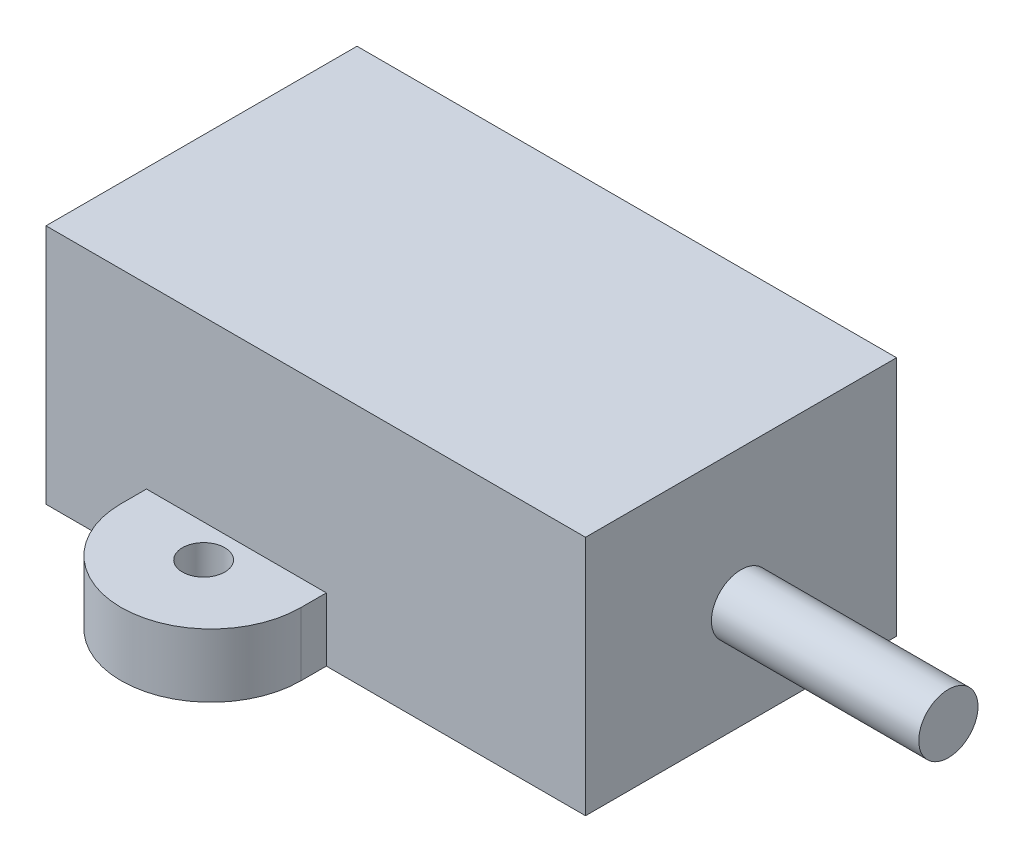
SolidWorks part; units mm, degrees
ref_plane "前视基准面" through (0, 0, 0) normal (0, 0, 1) x (1, 0, 0)
ref_plane "上视基准面" through (0, 0, 0) normal (0, 1, 0) x (1, 0, 0)
ref_plane "右视基准面" through (0, 0, 0) normal (1, 0, 0) x (0, 0, -1)
sketch "草图1" plane through (0, 0, 0) normal (0, 1, 0) x (1, 0, 0)
  line L1 (-12.75, 7.35) -> (12.75, 7.35)
  line L2 (-12.75, 7.35) -> (-12.75, -7.35)
  line L3 (-12.75, -7.35) -> (12.75, -7.35)
  line L4 (12.75, 7.35) -> (12.75, -7.35)
  line L5 (-12.75, 7.35) -> (12.75, -7.35) construction
  line L6 (-12.75, -7.35) -> (12.75, 7.35) construction
  point P0 (0, 0)
  dimension "D1" = 14.7
  dimension "D2" = 25.5
extrude "主体" add sketch "草图1" along normal blind 11.4
sketch "草图2" plane through (12.75, 0, 0) normal (1, 0, 0) x (0, 0, -1)
  line L0 (-7.35, 0) -> (7.35, 0) construction
  line L1 (0, 6.27) -> (0, -6.27) construction
  circle A0 centre (0, 5) radius 1.4
  point P2 (0, 0)
  point P5 (0, 0)
  point P8 (0, 0)
  dimension "D1" = 5
extrude "电机轴" add sketch "草图2" along normal blind 9.8
sketch "草图3" plane through (0, 0, 0) normal (0, -1, 0) x (1, 0, 0)
  line L0 (-3.75, -8.9) -> (-3.75, 8.9) construction
  line L1 (6.27, 0) -> (-6.27, 0) construction
  line L2 (12.75, 7.35) -> (12.75, -7.35) construction
  line L3 (-8, -7.35) -> (0.5, -7.35)
  line L4 (-8, -12.8) -> (0.5, -12.8)
  line L5 (-8, -12.8) -> (-8, 12.8) construction
  line L6 (-8, 12.8) -> (0.5, 12.8) construction
  line L7 (0.5, -12.8) -> (0.5, 12.8) construction
  line L8 (-8, -12.8) -> (0.5, 12.8) construction
  line L9 (-8, 12.8) -> (0.5, -12.8) construction
  line L10 (12.75, -7.35) -> (-12.75, -7.35) construction
  line L11 (-8, -12.8) -> (-8, -7.35)
  line L12 (0.5, -12.8) -> (0.5, -7.35)
  circle A0 centre (-3.75, -8.9) radius 1
  circle A1 centre (-3.75, 8.9) radius 1 construction
  point P3 (-3.75, 0)
  point P7 (-3.75, 0)
  dimension "D1" = 17.8
  dimension "D2" = 16.5
  dimension "D3" = 8.5
  dimension "D4" = 25.6
extrude "螺丝孔" add sketch "草图3" against normal blind 3
ref_axis "转轴" through (22.55, 5, 0) along (-1, 0, 0)
ref_plane "螺丝孔圆角切面" through (0, 0, -12.8) normal (0, 0, -1) x (-1, 0, 0)
fillet "圆角3" 2 edges at (-8, 1.5, -12.8) (0.5, 1.5, -12.8) type full round first side face at (-8, 1.5, -10.075) second side face at (0.5, 1.5, -10.075) middle face at (-3.75, 1.5, -12.8)
mirror "镜向3" about plane through (0, 0, 0) normal (0, 0, 1) of "圆角3", "螺丝孔"
